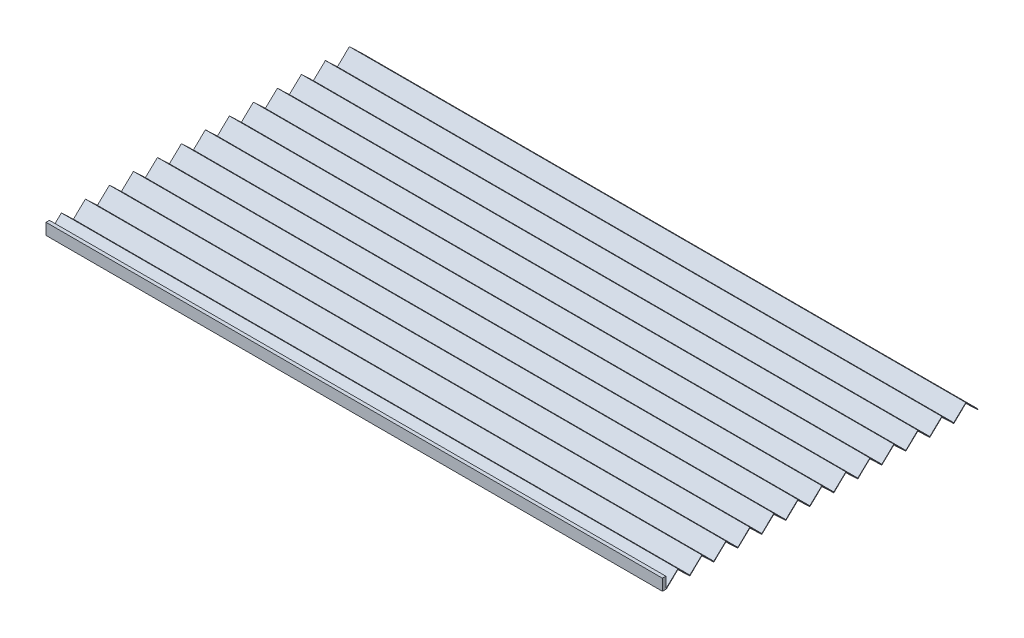
SolidWorks part; units mm, degrees
ref_plane "Front Plane" through (0, 0, 0) normal (0, 0, 1) x (1, 0, 0)
ref_plane "Top Plane" through (0, 0, 0) normal (0, 1, 0) x (1, 0, 0)
ref_plane "Right Plane" through (0, 0, 0) normal (1, 0, 0) x (0, 0, -1)
sketch "Sketch2" plane through (0, 0, 0) normal (0, 0, 1) x (1, 0, 0)
  line L1 (-270, 10) -> (270, 10)
  line L2 (-270, 10) -> (-270, 0)
  line L3 (-270, 0) -> (270, 0)
  line L4 (270, 10) -> (270, 0)
  point P4 (0, 0)
  dimension "D1" = 10
  dimension "D2" = 540
extrude "Boss-Extrude1" add sketch "Sketch2" along normal blind 3
sketch "Sketch3" plane through (270, 0, 0) normal (1, 0, 0) x (0, 0, -1)
  line L0 (0, 10) -> (273.2797, 10) construction
  line L1 (0, 0) -> (273.2797, 0) construction
  line L2 (273.2797, 10) -> (273.2797, 0) construction
  line L3 (0, 0) -> (10.5108, 10)
  line L4 (10.5108, 10) -> (21.0215, 0)
  line L5 (21.0215, 0) -> (31.5323, 10)
  line L6 (31.5323, 10) -> (42.043, 0)
  line L7 (42.043, 0) -> (52.5538, 10)
  line L8 (52.5538, 10) -> (63.0645, 0)
  line L9 (63.0645, 0) -> (73.5753, 10)
  line L10 (73.5753, 10) -> (84.0861, 0)
  line L11 (84.0861, 0) -> (94.5968, 10)
  line L12 (94.5968, 10) -> (105.1076, 0)
  line L13 (105.1076, 0) -> (115.6183, 10)
  line L14 (115.6183, 10) -> (126.1291, 0)
  line L15 (126.1291, 0) -> (136.6398, 10)
  line L16 (136.6398, 10) -> (147.1506, 0)
  line L17 (147.1506, 0) -> (157.6613, 10)
  line L18 (157.6613, 10) -> (168.1721, 0)
  line L20 (168.1721, 0) -> (178.6829, 10)
  line L21 (178.6829, 10) -> (189.1936, 0)
  line L22 (189.1936, 0) -> (199.7044, 10)
  line L23 (199.7044, 10) -> (210.2151, 0)
  line L24 (210.2151, 0) -> (220.7259, 10)
  line L25 (220.7259, 10) -> (231.2366, 0)
  line L26 (231.2366, 0) -> (241.7474, 10)
  line L27 (241.7474, 10) -> (252.2582, 0)
  line L28 (252.2582, 0) -> (262.7689, 10)
  line L29 (262.7689, 10) -> (273.2797, 0)
  line L30 (273.2797, 10) -> (273.2797, 0) construction
extrude "Extrude-Thin1" add sketch "Sketch3" against normal through all thin thin type mid plane wall 0.5
